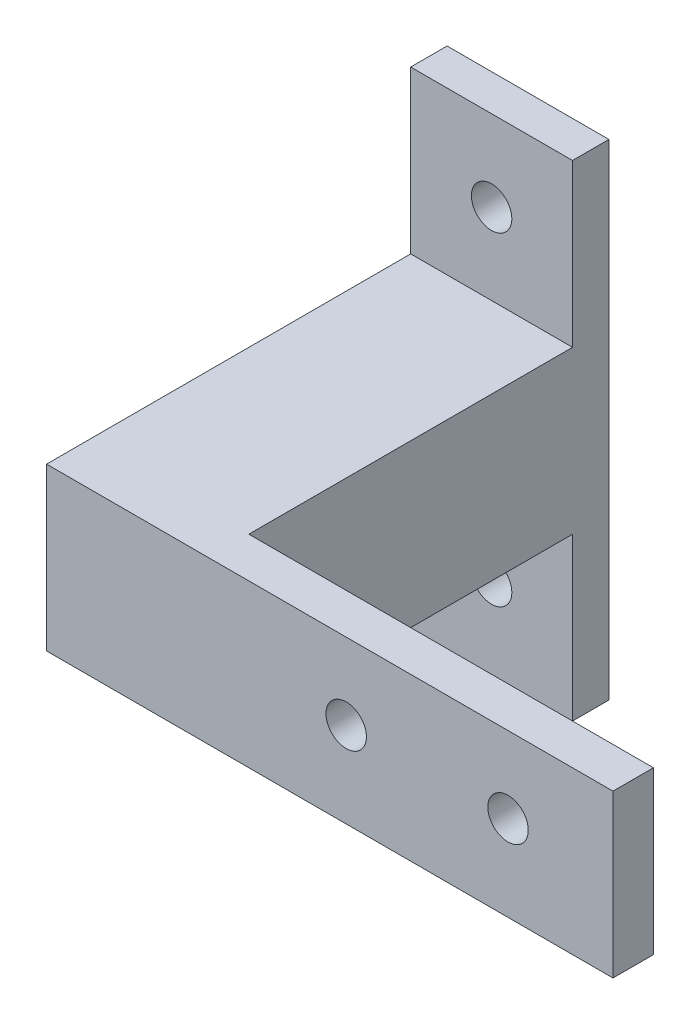
SolidWorks part; units mm, degrees
ref_plane "前视基准面" through (0, 0, 0) normal (0, 0, 1) x (1, 0, 0)
ref_plane "上视基准面" through (0, 0, 0) normal (0, 1, 0) x (1, 0, 0)
ref_plane "右视基准面" through (0, 0, 0) normal (1, 0, 0) x (0, 0, -1)
sketch "草图1" plane through (0, 0, 0) normal (0, 0, 1) x (1, 0, 0)
  line L1 (10, -30) -> (-10, -30)
  line L2 (10, -30) -> (10, 30)
  line L3 (10, 30) -> (-10, 30)
  line L4 (-10, -30) -> (-10, 30)
  line L5 (10, -30) -> (-10, 30) construction
  line L6 (10, 30) -> (-10, -30) construction
  point P0 (0, 0)
  dimension "D1" = 20
  dimension "D2" = 60
extrude "凸台-拉伸1" add sketch "草图1" along normal blind 4.5
sketch "草图2" plane through (0, 0, 4.5) normal (0, 0, 1) x (1, 0, 0)
  line L0 (-10, 30) -> (-10, -30) construction
  line L1 (10, -10) -> (-10, -10)
  line L2 (10, -10) -> (10, 10)
  line L3 (10, 10) -> (-10, 10)
  line L4 (-10, -10) -> (-10, 10)
  line L5 (10, -10) -> (-10, 10) construction
  line L6 (10, 10) -> (-10, -10) construction
  point P0 (0, 0)
  dimension "D1" = 20
extrude "凸台-拉伸2" add sketch "草图2" along normal blind 40
sketch "草图3" plane through (0, 0, 44.5) normal (0, 0, 1) x (1, 0, 0)
  line L1 (-10, -10) -> (60, -10)
  line L2 (-10, -10) -> (-10, 10)
  line L3 (-10, 10) -> (60, 10)
  line L4 (60, -10) -> (60, 10)
  dimension "D1" = 20
  dimension "D2" = 70
extrude "凸台-拉伸3" add sketch "草图3" along normal blind 5
sketch "草图4" plane through (0, 0, 44.5) normal (0, 0, -1) x (-1, 0, 0)
  circle A0 centre (-27.0299, 0.5689) radius 2.5
  circle A1 centre (-47.0299, 0.5689) radius 2.5
  dimension "D1" = 20
  dimension "D2" = 5
  dimension "D3" = 5
extrude "切除-拉伸1" cut sketch "草图4" against normal blind 5
sketch "草图5" plane through (0, 0, 4.5) normal (0, 0, 1) x (1, 0, 0)
  line L0 (-10, -10) -> (60, -10) construction
  line L1 (10, 10) -> (-10, 10) construction
  circle A0 centre (0, 20) radius 2.5
  circle A1 centre (0, -20) radius 2.5
  dimension "D1" = 10
  dimension "D2" = 10
  dimension "D3" = 5
  dimension "D4" = 5
extrude "切除-拉伸2" cut sketch "草图5" against normal blind 5
